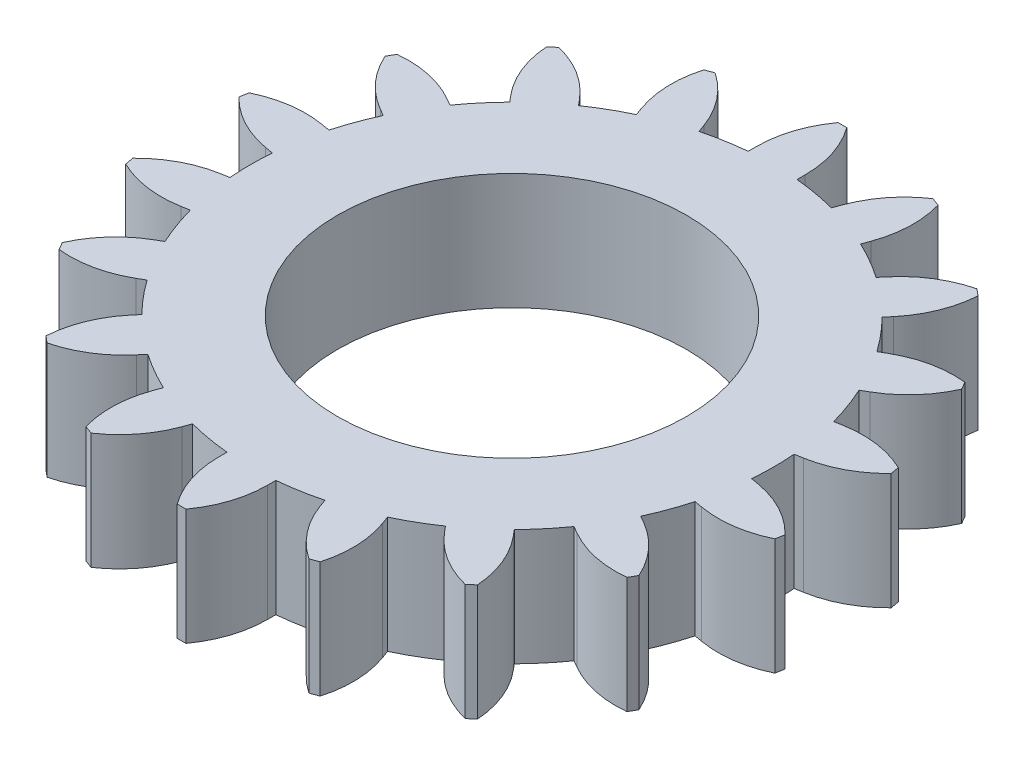
SolidWorks part; units mm, degrees
material "Magnesium Alloy"
ref_plane "Front Plane" through (0, 0, 0) normal (0, 0, 1) x (1, 0, 0)
ref_plane "Top Plane" through (0, 0, 0) normal (0, 1, 0) x (1, 0, 0)
ref_plane "Right Plane" through (0, 0, 0) normal (1, 0, 0) x (0, 0, -1)
sketch "Sketch1" plane through (0, 0, 0) normal (0, 1, 0) x (1, 0, 0)
  circle A0 centre (0, 0) radius 19.05
  circle A2 centre (0, 0) radius 12.7
  dimension "D1" = 38.1
  dimension "D2" = 25.4
extrude "Boss-Extrude1" add sketch "Sketch1" along normal blind 8.4658
sketch "Sketch2" plane through (0, 0, 0) normal (0, 1, 0) x (1, 0, 0)
  line L0 (-1.778, 18.9668) -> (-1.778, 22.1418)
  line L1 (-1.778, 22.1418) -> (-0.3175, 24.0468)
  line L2 (-0.3175, 24.0468) -> (0.3175, 24.0468)
  line L3 (0.3175, 24.0468) -> (1.778, 22.1418)
  line L4 (1.778, 22.1418) -> (1.778, 18.9668)
  line L5 (0, -4.6562) -> (0, 4.6562) construction
  circle A0 centre (0, 0) radius 19.05 construction
  arc A1 (1.778, 18.9668) -> (-1.778, 18.9668) centre (0, 0) ccw
  dimension "D1" = 3.175
  dimension "D2" = 1.905
  dimension "D3" = 1.778
  dimension "D4" = 1.778
  dimension "D5" = 0.635
extrude "Boss-Extrude2" add sketch "Sketch2" along normal blind 8.4658
pattern_circular "CirPattern1" count 18 over 360 about axis through (0, 8.4658, 0) along (0, 1, 0) of "Boss-Extrude2"
fillet "Fillet2" radius 7.62 36 edges at (1.778, 4.2329, -22.1418) (-1.778, 4.2329, -22.1418) (22.1142, 4.2329, 2.0939) (21.4967, 4.2329, -5.5959) (20.0644, 4.2329, 9.5311) (15.5945, 4.2329, 15.8188) (20.0644, 4.2329, -9.5311) (22.1142, 4.2329, -2.0939) (21.4967, 4.2329, 5.5959) (18.2864, 4.2329, 12.6107) (12.8705, 4.2329, 18.1045) (5.9022, 4.2329, 21.4146) (-1.778, 4.2329, 22.1418) (9.2437, 4.2329, 20.1984) (1.778, 4.2329, 22.1418) (-5.9022, 4.2329, 21.4146) (-12.8705, 4.2329, 18.1045) (-9.2437, 4.2329, 20.1984) (-15.5945, 4.2329, 15.8188) (-20.0644, 4.2329, 9.5311) (-22.1142, 4.2329, 2.0939) (-18.2864, 4.2329, 12.6107) (-21.4967, 4.2329, 5.5959) (-22.1142, 4.2329, -2.0939) (-20.0644, 4.2329, -9.5311) (-15.5945, 4.2329, -15.8188) (-9.2437, 4.2329, -20.1984) (5.9022, 4.2329, -21.4146) (12.8705, 4.2329, -18.1045) (18.2864, 4.2329, -12.6107) (-21.4967, 4.2329, -5.5959) (15.5945, 4.2329, -15.8188) (-18.2864, 4.2329, -12.6107) (-12.8705, 4.2329, -18.1045) (9.2437, 4.2329, -20.1984) (-5.9022, 4.2329, -21.4146)
